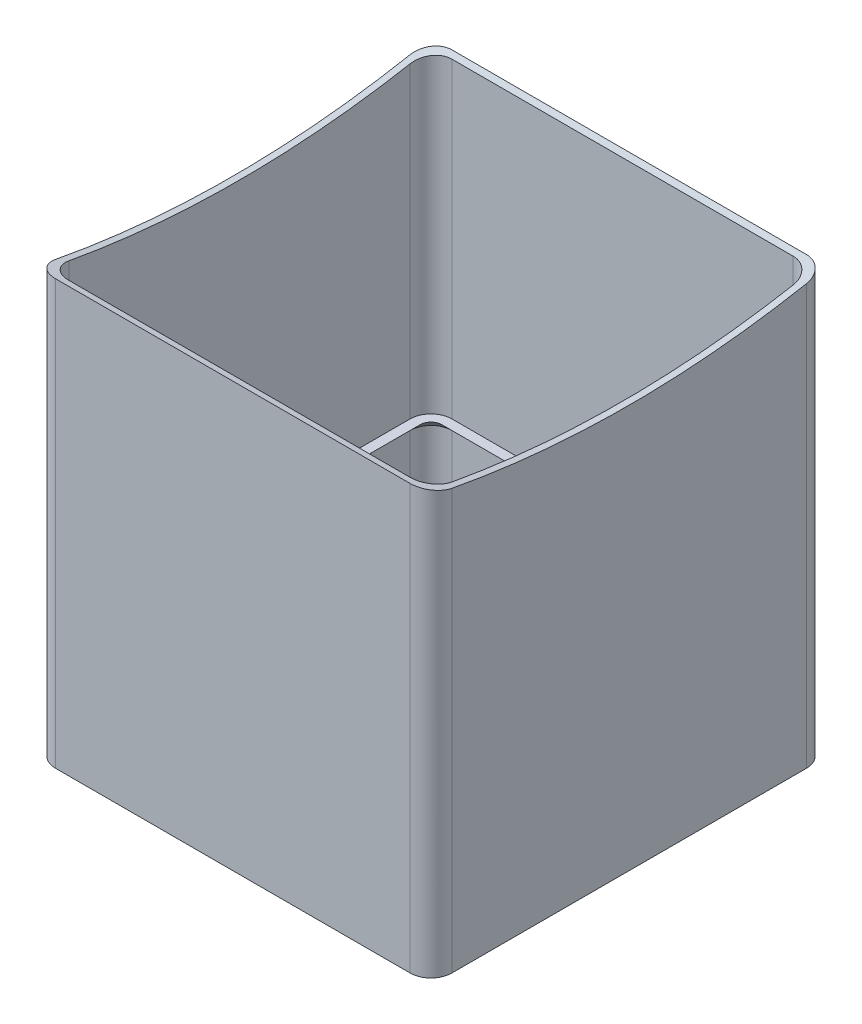
SolidWorks part; units mm, degrees
ref_plane "Front Plane" through (0, 0, 0) normal (0, 0, 1) x (1, 0, 0)
ref_plane "Top Plane" through (0, 0, 0) normal (0, 1, 0) x (1, 0, 0)
ref_plane "Right Plane" through (0, 0, 0) normal (1, 0, 0) x (0, 0, -1)
sketch "Sketch1" plane through (0, 0, 0) normal (0, 1, 0) x (1, 0, 0)
  line L1 (-47.5, -47.5) -> (47.5, -47.5)
  line L2 (-47.5, -47.5) -> (-47.5, 47.5)
  line L3 (-47.5, 47.5) -> (47.5, 47.5)
  line L4 (47.5, -47.5) -> (47.5, 47.5)
  line L5 (-47.5, -47.5) -> (47.5, 47.5) construction
  line L6 (-47.5, 47.5) -> (47.5, -47.5) construction
  point P0 (0, 0)
  dimension "D1" = 95
  dimension "D2" = 95
extrude "Boss-Extrude1" add sketch "Sketch1" along normal blind 1.6
sketch "Sketch2" plane through (0, 1.6, 0) normal (0, 1, 0) x (1, 0, 0)
  line L8 (45.9, -45.9) -> (45.9, 45.9)
  line L9 (45.9, 45.9) -> (-45.9, 45.9)
  line L10 (-45.9, 45.9) -> (-45.9, -45.9)
  line L11 (-45.9, -45.9) -> (45.9, -45.9)
  line L12 (45.9, -45.9) -> (45.9, 45.9)
  line L13 (45.9, 45.9) -> (-45.9, 45.9)
  line L14 (-45.9, 45.9) -> (-45.9, -45.9)
  line L15 (-45.9, -45.9) -> (45.9, -45.9)
  line L16 (47.5, -47.5) -> (47.5, 47.5)
  line L17 (47.5, 47.5) -> (-47.5, 47.5)
  line L18 (-47.5, 47.5) -> (-47.5, -47.5)
  line L19 (-47.5, -47.5) -> (47.5, -47.5)
  line L20 (47.5, -47.5) -> (47.5, 47.5)
  line L21 (47.5, 47.5) -> (-47.5, 47.5)
  line L22 (-47.5, 47.5) -> (-47.5, -47.5)
  line L23 (-47.5, -47.5) -> (47.5, -47.5)
  dimension "D1" = 1.6
  dimension "D2" = 0
extrude "Boss-Extrude2" add sketch "Sketch2" along normal blind 100
sketch "Sketch3" plane through (47.5, 0, 0) normal (1, 0, 0) x (0, 0, -1)
  line L0 (-47.5, 101.6) -> (47.5, 101.6) construction
  line L1 (-47.5, 101.6) -> (47.5, 101.6)
  arc A0 (-47.5, 101.6) -> (47.5, 101.6) centre (0, 324.725) ccw
  point P3 (0, 96.6)
  dimension "D1" = 5
extrude "Cut-Extrude1" cut sketch "Sketch3" against normal through all
fillet "Fillet1" radius 5 8 edges at (47.5, 50.8, 47.5) (-47.5, 50.8, -47.5) (47.5, 50.8, -47.5) (45.9, 51.4327, 45.9) (45.9, 51.4327, -45.9) (-45.9, 51.4327, -45.9) (-45.9, 51.4327, 45.9) (-47.5, 50.8, 47.5)
sketch "Sketch4" plane through (-47.5, 0, 0) normal (-1, 0, 0) x (0, 0, 1)
  line L0 (-42.5, 0) -> (42.5, 0) construction
  line L1 (-26.5, 22) -> (26.5, 22)
  line L2 (-26.5, 22) -> (-26.5, 0)
  line L3 (-26.5, 0) -> (26.5, 0)
  line L4 (26.5, 22) -> (26.5, 0)
  line L5 (-26.5, 22) -> (26.5, 0) construction
  line L6 (-26.5, 0) -> (26.5, 22) construction
  point P0 (0, 11)
  dimension "D1" = 53
  dimension "D2" = 22
extrude "Cut-Extrude2" cut sketch "Sketch4" against normal blind 1.6
sketch "Sketch5" plane through (0, 1.6, 0) normal (0, 1, 0) x (1, 0, 0)
  line L0 (-45.9, 40.9) -> (-45.9, 26.5) construction
  line L1 (-22.4, -24.5) -> (35.6, -24.5) construction
  line L2 (-22.4, -24.5) -> (-22.4, 24.5) construction
  line L3 (-22.4, 24.5) -> (35.6, 24.5) construction
  line L4 (35.6, -24.5) -> (35.6, 24.5) construction
  line L5 (-22.4, -24.5) -> (35.6, 24.5) construction
  line L6 (-22.4, 24.5) -> (35.6, -24.5) construction
  circle A0 centre (-22.4, 24.5) radius 1.65
  circle A1 centre (35.6, 24.5) radius 1.65
  circle A2 centre (35.6, -24.5) radius 1.65
  circle A3 centre (-22.4, -24.5) radius 1.65
  point P0 (6.6, 0)
  dimension "D4" = 3.3
  dimension "D1" = 58
  dimension "D2" = 49
  dimension "D3" = 23.5
extrude "Cut-Extrude3" cut sketch "Sketch5" against normal through all
sketch "Sketch6" plane through (0, 0, -47.5) normal (0, 0, -1) x (-1, 0, 0)
  line L0 (-42.5, 0) -> (42.5, 0) construction
  line L1 (-36.6, 0) -> (23.4, 0)
  line L2 (-36.6, 0) -> (-36.6, 15)
  line L3 (-36.6, 15) -> (23.4, 15)
  line L4 (23.4, 0) -> (23.4, 15)
  line L5 (-36.6, 0) -> (23.4, 15) construction
  line L6 (-36.6, 15) -> (23.4, 0) construction
  line L7 (24.05, 1.6) -> (20.75, 1.6) construction
  line L8 (-33.95, 1.6) -> (-37.25, 1.6) construction
  line L9 (24.05, 1.6) -> (20.75, 1.6) construction
  line L10 (-33.95, 1.6) -> (-37.25, 1.6) construction
  line L11 (-35.6, 1.6) -> (22.4, 1.6) construction
  point P0 (-6.6, 7.5)
  point P12 (-35.6, 1.6)
  point P13 (22.4, 1.6)
  point P16 (-6.6, 1.6)
  dimension "D1" = 15
  dimension "D2" = 60
extrude "Cut-Extrude4" cut sketch "Sketch6" against normal blind 1.6
fillet "Fillet2" radius 5 2 edges at (36.6, 15, -46.7) (-23.4, 15, -46.7)
sketch "Sketch7" plane through (0, 1.6, 0) normal (0, 1, 0) x (1, 0, 0)
  line L8 (-40.9, -45.9) -> (40.9, -45.9)
  line L9 (45.9, -40.9) -> (45.9, 40.9)
  line L10 (40.9, 45.9) -> (36.6, 45.9)
  line L11 (36.6, 45.9) -> (-23.4, 45.9)
  line L12 (-23.4, 45.9) -> (-40.9, 45.9)
  line L13 (-45.9, 40.9) -> (-45.9, 26.5)
  line L14 (-45.9, 26.5) -> (-45.9, -26.5)
  line L15 (-45.9, -26.5) -> (-45.9, -40.9)
  line L16 (-40.9, -45.9) -> (40.9, -45.9)
  line L17 (45.9, -40.9) -> (45.9, 40.9)
  line L18 (40.9, 45.9) -> (36.6, 45.9)
  line L19 (36.6, 45.9) -> (-23.4, 45.9)
  line L20 (-23.4, 45.9) -> (-40.9, 45.9)
  line L21 (-45.9, 40.9) -> (-45.9, 26.5)
  line L22 (-45.9, 26.5) -> (-45.9, -26.5)
  line L23 (-45.9, -26.5) -> (-45.9, -40.9)
  line L40 (-40.9, -43.5) -> (40.9, -43.5)
  line L41 (43.5, -40.9) -> (43.5, 40.9)
  line L42 (40.9, 43.5) -> (36.6, 43.5)
  line L43 (36.6, 43.5) -> (-23.4, 43.5)
  line L44 (-23.4, 43.5) -> (-40.9, 43.5)
  line L45 (-43.5, 40.9) -> (-43.5, 26.5)
  line L46 (-43.5, 26.5) -> (-43.5, -26.5)
  line L47 (-43.5, -26.5) -> (-43.5, -40.9)
  line L48 (-40.9, -43.5) -> (40.9, -43.5)
  line L49 (43.5, -40.9) -> (43.5, 40.9)
  line L50 (40.9, 43.5) -> (36.6, 43.5)
  line L51 (36.6, 43.5) -> (-23.4, 43.5)
  line L52 (-23.4, 43.5) -> (-40.9, 43.5)
  line L53 (-43.5, 40.9) -> (-43.5, 26.5)
  line L54 (-43.5, 26.5) -> (-43.5, -26.5)
  line L55 (-43.5, -26.5) -> (-43.5, -40.9)
  arc A4 (40.9, -45.9) -> (45.9, -40.9) centre (40.9, -40.9) ccw
  arc A5 (45.9, 40.9) -> (40.9, 45.9) centre (40.9, 40.9) ccw
  arc A6 (-40.9, 45.9) -> (-45.9, 40.9) centre (-40.9, 40.9) ccw
  arc A7 (-45.9, -40.9) -> (-40.9, -45.9) centre (-40.9, -40.9) ccw
  arc A8 (40.9, -45.9) -> (45.9, -40.9) centre (40.9, -40.9) ccw
  arc A9 (45.9, 40.9) -> (40.9, 45.9) centre (40.9, 40.9) ccw
  arc A10 (-40.9, 45.9) -> (-45.9, 40.9) centre (-40.9, 40.9) ccw
  arc A11 (-45.9, -40.9) -> (-40.9, -45.9) centre (-40.9, -40.9) ccw
  arc A20 (40.9, -43.5) -> (43.5, -40.9) centre (40.9, -40.9) ccw
  arc A21 (43.5, 40.9) -> (40.9, 43.5) centre (40.9, 40.9) ccw
  arc A22 (-40.9, 43.5) -> (-43.5, 40.9) centre (-40.9, 40.9) ccw
  arc A23 (-43.5, -40.9) -> (-40.9, -43.5) centre (-40.9, -40.9) ccw
  arc A24 (40.9, -43.5) -> (43.5, -40.9) centre (40.9, -40.9) ccw
  arc A25 (43.5, 40.9) -> (40.9, 43.5) centre (40.9, 40.9) ccw
  arc A26 (-40.9, 43.5) -> (-43.5, 40.9) centre (-40.9, 40.9) ccw
  arc A27 (-43.5, -40.9) -> (-40.9, -43.5) centre (-40.9, -40.9) ccw
  dimension "D1" = 0
  dimension "D2" = 2.4
extrude "Boss-Extrude3" add sketch "Sketch7" against normal blind 2.4 from offset 25
chamfer "Chamfer1" distance 2.4 angle 45 8 edges at (0, 24.2, 43.5) (42.7385, 24.2, 42.7385) (-42.7385, 24.2, 42.7385) (43.5, 24.2, 0) (-43.5, 24.2, 0) (42.7385, 24.2, -42.7385) (-42.7385, 24.2, -42.7385) (0, 24.2, -43.5)
